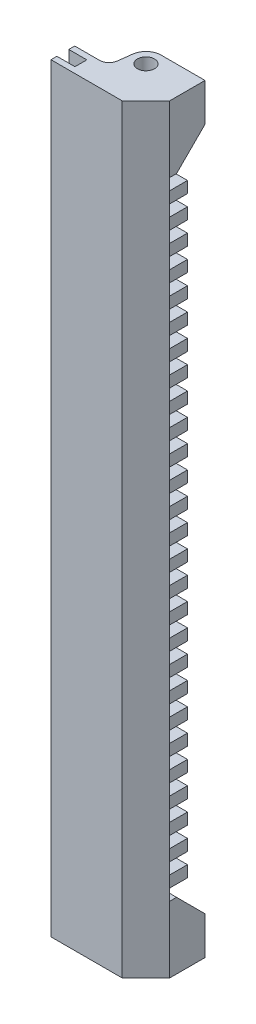
SolidWorks part; units mm, degrees
ref_plane "Front Plane" through (0, 0, 0) normal (0, 0, 1) x (1, 0, 0)
ref_plane "Top Plane" through (0, 0, 0) normal (0, 1, 0) x (1, 0, 0)
ref_plane "Right Plane" through (0, 0, 0) normal (1, 0, 0) x (0, 0, -1)
sketch "Sketch1" plane through (0, 0, 0) normal (0, 1, 0) x (1, 0, 0)
  line L0 (0, 0) -> (25.4, 0)
  line L1 (25.4, 0) -> (25.4, 25.4)
  line L2 (25.4, 25.4) -> (19.05, 25.4)
  line L3 (19.05, 25.4) -> (19.05, 6.35)
  line L4 (19.05, 6.35) -> (0, 6.35)
  line L5 (0, 6.35) -> (0, 0)
  dimension "D1" = 25.4
  dimension "D2" = 6.35
extrude "Boss-Extrude1" add sketch "Sketch1" along normal blind 203.2
sketch "Sketch2" plane through (0, 203.2, 0) normal (0, 1, 0) x (1, 0, 0)
  line L0 (19.05, 25.4) -> (19.05, 6.35) construction
  line L1 (19.05, 6.35) -> (0, 6.35) construction
  line L2 (19.05, 15.8022) -> (19.05, 6.35)
  line L3 (19.05, 6.35) -> (8.89, 6.35)
  line L4 (8.89, 6.35) -> (9.6295, 12.244)
  line L5 (19.05, 15.8022) -> (13.6618, 15.8022)
  line L6 (13.6618, 11.7382) -> (19.05, 6.35) construction
  arc A0 (13.6618, 15.8022) -> (9.6295, 12.244) centre (13.6618, 11.7382) ccw
  circle A1 centre (13.6618, 11.7382) radius 2.286
  dimension "D4" = 4.572
  dimension "D5" = 1.778
  dimension "D1" = 45
  dimension "D3" = 10.16
  dimension "D6" = 7.62
extrude "Boss-Extrude2" add sketch "Sketch2" against normal blind 6.35
ref_plane "Plane1" through (0, 101.6, 0) normal (0, 1, 0) x (1, 0, 0)
fillet "Fillet1" radius 2.54 1 edges at (8.89, 200.025, -6.35)
mirror "Mirror1" about plane through (0, 101.6, 0) normal (0, 1, 0) of "Fillet1", "Boss-Extrude2"
sketch "Sketch5" plane through (0, 203.2, 0) normal (0, 1, 0) x (1, 0, 0)
  line L0 (25.4, 0) -> (25.4, 25.4) construction
  line L1 (19.05, 25.4) -> (25.4, 25.4)
  line L2 (19.05, 25.4) -> (19.05, 15.8022)
  line L3 (19.05, 15.8022) -> (25.4, 15.8022)
  line L4 (25.4, 25.4) -> (25.4, 15.8022)
extrude "Cut-Extrude3" cut sketch "Sketch5" against normal through all
sketch "Sketch4" plane through (0, 0, 0) normal (0, -1, 0) x (1, 0, 0)
  line L0 (0, -6.35) -> (0, 0) construction
  line L1 (0, -1.5875) -> (4.826, -1.5875)
  line L2 (0, -1.5875) -> (0, -4.7625)
  line L3 (0, -4.7625) -> (4.826, -4.7625)
  line L4 (4.826, -1.5875) -> (4.826, -4.7625)
  point P6 (0, -3.175)
  point P7 (0, -3.175)
  dimension "D1" = 3.175
  dimension "D2" = 4.826
extrude "Cut-Extrude2" cut sketch "Sketch4" against normal through all
sketch "Sketch6" plane through (19.05, 0, 0) normal (-1, 0, 0) x (0, 0, 1)
  line L0 (-6.35, 196.85) -> (-6.35, 6.35) construction
  line L1 (-6.35, 17.78) -> (-15.8022, 17.78)
  line L2 (-6.35, 17.78) -> (-6.35, 20.828)
  line L3 (-6.35, 20.828) -> (-15.8022, 20.828)
  line L4 (-15.8022, 17.78) -> (-15.8022, 20.828)
  line L5 (-15.8022, 6.35) -> (-15.8022, 196.85) construction
  line L6 (-6.35, 23.876) -> (-6.35, 26.924)
  line L7 (-6.35, 23.876) -> (-15.8022, 23.876)
  line L8 (-15.8022, 23.876) -> (-15.8022, 26.924)
  line L9 (-6.35, 26.924) -> (-15.8022, 26.924)
  line L10 (-6.35, 29.972) -> (-6.35, 33.02)
  line L11 (-6.35, 29.972) -> (-15.8022, 29.972)
  line L12 (-15.8022, 29.972) -> (-15.8022, 33.02)
  line L13 (-6.35, 33.02) -> (-15.8022, 33.02)
  line L14 (-6.35, 36.068) -> (-6.35, 39.116)
  line L15 (-6.35, 36.068) -> (-15.8022, 36.068)
  line L16 (-15.8022, 36.068) -> (-15.8022, 39.116)
  line L17 (-6.35, 39.116) -> (-15.8022, 39.116)
  line L18 (-6.35, 42.164) -> (-6.35, 45.212)
  line L19 (-6.35, 42.164) -> (-15.8022, 42.164)
  line L20 (-15.8022, 42.164) -> (-15.8022, 45.212)
  line L21 (-6.35, 45.212) -> (-15.8022, 45.212)
  line L22 (-6.35, 48.26) -> (-6.35, 51.308)
  line L23 (-6.35, 48.26) -> (-15.8022, 48.26)
  line L24 (-15.8022, 48.26) -> (-15.8022, 51.308)
  line L25 (-6.35, 51.308) -> (-15.8022, 51.308)
  line L26 (-6.35, 54.356) -> (-6.35, 57.404)
  line L27 (-6.35, 54.356) -> (-15.8022, 54.356)
  line L28 (-15.8022, 54.356) -> (-15.8022, 57.404)
  line L29 (-6.35, 57.404) -> (-15.8022, 57.404)
  line L30 (-6.35, 60.452) -> (-6.35, 63.5)
  line L31 (-6.35, 60.452) -> (-15.8022, 60.452)
  line L32 (-15.8022, 60.452) -> (-15.8022, 63.5)
  line L33 (-6.35, 63.5) -> (-15.8022, 63.5)
  line L34 (-6.35, 66.548) -> (-6.35, 69.596)
  line L35 (-6.35, 66.548) -> (-15.8022, 66.548)
  line L36 (-15.8022, 66.548) -> (-15.8022, 69.596)
  line L37 (-6.35, 69.596) -> (-15.8022, 69.596)
  line L38 (-6.35, 72.644) -> (-6.35, 75.692)
  line L39 (-6.35, 72.644) -> (-15.8022, 72.644)
  line L40 (-15.8022, 72.644) -> (-15.8022, 75.692)
  line L41 (-6.35, 75.692) -> (-15.8022, 75.692)
  line L42 (-6.35, 78.74) -> (-6.35, 81.788)
  line L43 (-6.35, 78.74) -> (-15.8022, 78.74)
  line L44 (-15.8022, 78.74) -> (-15.8022, 81.788)
  line L45 (-6.35, 81.788) -> (-15.8022, 81.788)
  line L46 (-6.35, 84.836) -> (-6.35, 87.884)
  line L47 (-6.35, 84.836) -> (-15.8022, 84.836)
  line L48 (-15.8022, 84.836) -> (-15.8022, 87.884)
  line L49 (-6.35, 87.884) -> (-15.8022, 87.884)
  line L50 (-6.35, 90.932) -> (-6.35, 93.98)
  line L51 (-6.35, 90.932) -> (-15.8022, 90.932)
  line L52 (-15.8022, 90.932) -> (-15.8022, 93.98)
  line L53 (-6.35, 93.98) -> (-15.8022, 93.98)
  line L54 (-6.35, 97.028) -> (-6.35, 100.076)
  line L55 (-6.35, 97.028) -> (-15.8022, 97.028)
  line L56 (-15.8022, 97.028) -> (-15.8022, 100.076)
  line L57 (-6.35, 100.076) -> (-15.8022, 100.076)
  line L58 (-6.35, 103.124) -> (-6.35, 106.172)
  line L59 (-6.35, 103.124) -> (-15.8022, 103.124)
  line L60 (-15.8022, 103.124) -> (-15.8022, 106.172)
  line L61 (-6.35, 106.172) -> (-15.8022, 106.172)
  line L62 (-6.35, 109.22) -> (-6.35, 112.268)
  line L63 (-6.35, 109.22) -> (-15.8022, 109.22)
  line L64 (-15.8022, 109.22) -> (-15.8022, 112.268)
  line L65 (-6.35, 112.268) -> (-15.8022, 112.268)
  line L66 (-6.35, 115.316) -> (-6.35, 118.364)
  line L67 (-6.35, 115.316) -> (-15.8022, 115.316)
  line L68 (-15.8022, 115.316) -> (-15.8022, 118.364)
  line L69 (-6.35, 118.364) -> (-15.8022, 118.364)
  line L70 (-6.35, 121.412) -> (-6.35, 124.46)
  line L71 (-6.35, 121.412) -> (-15.8022, 121.412)
  line L72 (-15.8022, 121.412) -> (-15.8022, 124.46)
  line L73 (-6.35, 124.46) -> (-15.8022, 124.46)
  line L74 (-6.35, 127.508) -> (-6.35, 130.556)
  line L75 (-6.35, 127.508) -> (-15.8022, 127.508)
  line L76 (-15.8022, 127.508) -> (-15.8022, 130.556)
  line L77 (-6.35, 130.556) -> (-15.8022, 130.556)
  line L78 (-6.35, 133.604) -> (-6.35, 136.652)
  line L79 (-6.35, 133.604) -> (-15.8022, 133.604)
  line L80 (-15.8022, 133.604) -> (-15.8022, 136.652)
  line L81 (-6.35, 136.652) -> (-15.8022, 136.652)
  line L82 (-6.35, 139.7) -> (-6.35, 142.748)
  line L83 (-6.35, 139.7) -> (-15.8022, 139.7)
  line L84 (-15.8022, 139.7) -> (-15.8022, 142.748)
  line L85 (-6.35, 142.748) -> (-15.8022, 142.748)
  line L86 (-6.35, 145.796) -> (-6.35, 148.844)
  line L87 (-6.35, 145.796) -> (-15.8022, 145.796)
  line L88 (-15.8022, 145.796) -> (-15.8022, 148.844)
  line L89 (-6.35, 148.844) -> (-15.8022, 148.844)
  line L90 (-6.35, 151.892) -> (-6.35, 154.94)
  line L91 (-6.35, 151.892) -> (-15.8022, 151.892)
  line L92 (-15.8022, 151.892) -> (-15.8022, 154.94)
  line L93 (-6.35, 154.94) -> (-15.8022, 154.94)
  line L94 (-6.35, 157.988) -> (-6.35, 161.036)
  line L95 (-6.35, 157.988) -> (-15.8022, 157.988)
  line L96 (-15.8022, 157.988) -> (-15.8022, 161.036)
  line L97 (-6.35, 161.036) -> (-15.8022, 161.036)
  line L98 (-6.35, 164.084) -> (-6.35, 167.132)
  line L99 (-6.35, 164.084) -> (-15.8022, 164.084)
  line L100 (-15.8022, 164.084) -> (-15.8022, 167.132)
  line L101 (-6.35, 167.132) -> (-15.8022, 167.132)
  line L102 (-6.35, 170.18) -> (-6.35, 173.228)
  line L103 (-6.35, 170.18) -> (-15.8022, 170.18)
  line L104 (-15.8022, 170.18) -> (-15.8022, 173.228)
  line L105 (-6.35, 173.228) -> (-15.8022, 173.228)
  line L106 (-6.35, 176.276) -> (-6.35, 179.324)
  line L107 (-6.35, 176.276) -> (-15.8022, 176.276)
  line L108 (-15.8022, 176.276) -> (-15.8022, 179.324)
  line L109 (-6.35, 179.324) -> (-15.8022, 179.324)
  line L110 (-6.35, 182.372) -> (-6.35, 185.42)
  line L111 (-6.35, 182.372) -> (-15.8022, 182.372)
  line L112 (-15.8022, 182.372) -> (-15.8022, 185.42)
  line L113 (-6.35, 185.42) -> (-15.8022, 185.42)
  line L114 (-15.8022, 17.78) -> (-15.8022, 185.42) construction
  point P8 (-6.35, 101.6)
  point P9 (-15.8022, 101.6)
  dimension "D1" = 3.048
  dimension "D2" = 28
  dimension "D3" = 3.048
extrude "Cut-Extrude4" cut sketch "Sketch6" against normal through all
sketch "Sketch7" plane through (19.05, 0, 0) normal (-1, 0, 0) x (0, 0, 1)
  line L0 (-15.8022, 182.372) -> (-6.35, 182.372) construction
  line L1 (-15.8022, 20.828) -> (-11.1125, 20.828)
  line L2 (-15.8022, 20.828) -> (-15.8022, 182.372)
  line L3 (-15.8022, 182.372) -> (-11.1125, 182.372)
  line L4 (-11.1125, 20.828) -> (-11.1125, 182.372)
  line L5 (-6.35, 182.372) -> (-6.35, 179.324) construction
  dimension "D1" = 4.7625
extrude "Cut-Extrude5" cut sketch "Sketch7" against normal through all
chamfer "Chamfer1" distance 6.35 angle 45 1 edges at (25.4, 101.6, 0)
sketch "Sketch8" plane through (19.05, 0, 0) normal (-1, 0, 0) x (0, 0, 1)
  line L0 (-6.35, 182.372) -> (-11.1125, 182.372) construction
  line L1 (-11.1125, 182.372) -> (-11.1125, 179.324) construction
  line L2 (-11.1125, 179.324) -> (-6.35, 179.324) construction
  line L3 (-6.35, 179.324) -> (-6.35, 182.372) construction
  line L4 (-6.35, 176.276) -> (-11.1125, 176.276) construction
  line L5 (-11.1125, 176.276) -> (-11.1125, 173.228) construction
  line L6 (-11.1125, 173.228) -> (-6.35, 173.228) construction
  line L7 (-6.35, 173.228) -> (-6.35, 176.276) construction
  line L8 (-6.35, 170.18) -> (-11.1125, 170.18) construction
  line L9 (-11.1125, 170.18) -> (-11.1125, 167.132) construction
  line L10 (-11.1125, 167.132) -> (-6.35, 167.132) construction
  line L11 (-6.35, 167.132) -> (-6.35, 170.18) construction
  line L12 (-6.35, 164.084) -> (-11.1125, 164.084) construction
  line L13 (-11.1125, 164.084) -> (-11.1125, 161.036) construction
  line L14 (-11.1125, 161.036) -> (-6.35, 161.036) construction
  line L15 (-6.35, 161.036) -> (-6.35, 164.084) construction
  line L16 (-6.35, 157.988) -> (-11.1125, 157.988) construction
  line L17 (-11.1125, 157.988) -> (-11.1125, 154.94) construction
  line L18 (-11.1125, 154.94) -> (-6.35, 154.94) construction
  line L19 (-6.35, 154.94) -> (-6.35, 157.988) construction
  line L20 (-6.35, 151.892) -> (-11.1125, 151.892) construction
  line L21 (-11.1125, 151.892) -> (-11.1125, 148.844) construction
  line L22 (-11.1125, 148.844) -> (-6.35, 148.844) construction
  line L23 (-6.35, 148.844) -> (-6.35, 151.892) construction
  line L24 (-6.35, 145.796) -> (-11.1125, 145.796) construction
  line L25 (-11.1125, 145.796) -> (-11.1125, 142.748) construction
  line L26 (-11.1125, 142.748) -> (-6.35, 142.748) construction
  line L27 (-6.35, 142.748) -> (-6.35, 145.796) construction
  line L28 (-6.35, 139.7) -> (-11.1125, 139.7) construction
  line L29 (-11.1125, 139.7) -> (-11.1125, 136.652) construction
  line L30 (-11.1125, 136.652) -> (-6.35, 136.652) construction
  line L31 (-6.35, 136.652) -> (-6.35, 139.7) construction
  line L32 (-6.35, 133.604) -> (-11.1125, 133.604) construction
  line L33 (-11.1125, 133.604) -> (-11.1125, 130.556) construction
  line L34 (-11.1125, 130.556) -> (-6.35, 130.556) construction
  line L35 (-6.35, 130.556) -> (-6.35, 133.604) construction
  line L36 (-6.35, 127.508) -> (-11.1125, 127.508) construction
  line L37 (-11.1125, 127.508) -> (-11.1125, 124.46) construction
  line L38 (-11.1125, 124.46) -> (-6.35, 124.46) construction
  line L39 (-6.35, 124.46) -> (-6.35, 127.508) construction
  line L40 (-6.35, 121.412) -> (-11.1125, 121.412) construction
  line L41 (-11.1125, 121.412) -> (-11.1125, 118.364) construction
  line L42 (-11.1125, 118.364) -> (-6.35, 118.364) construction
  line L43 (-6.35, 118.364) -> (-6.35, 121.412) construction
  line L44 (-6.35, 115.316) -> (-11.1125, 115.316) construction
  line L45 (-11.1125, 115.316) -> (-11.1125, 112.268) construction
  line L46 (-11.1125, 112.268) -> (-6.35, 112.268) construction
  line L47 (-6.35, 112.268) -> (-6.35, 115.316) construction
  line L48 (-6.35, 109.22) -> (-11.1125, 109.22) construction
  line L49 (-11.1125, 109.22) -> (-11.1125, 106.172) construction
  line L50 (-11.1125, 106.172) -> (-6.35, 106.172) construction
  line L51 (-6.35, 106.172) -> (-6.35, 109.22) construction
  line L52 (-6.35, 103.124) -> (-11.1125, 103.124) construction
  line L53 (-11.1125, 103.124) -> (-11.1125, 100.076) construction
  line L54 (-11.1125, 100.076) -> (-6.35, 100.076) construction
  line L55 (-6.35, 100.076) -> (-6.35, 103.124) construction
  line L56 (-6.35, 97.028) -> (-11.1125, 97.028) construction
  line L57 (-11.1125, 97.028) -> (-11.1125, 93.98) construction
  line L58 (-11.1125, 93.98) -> (-6.35, 93.98) construction
  line L59 (-6.35, 93.98) -> (-6.35, 97.028) construction
  line L60 (-6.35, 90.932) -> (-11.1125, 90.932) construction
  line L61 (-11.1125, 90.932) -> (-11.1125, 87.884) construction
  line L62 (-11.1125, 87.884) -> (-6.35, 87.884) construction
  line L63 (-6.35, 87.884) -> (-6.35, 90.932) construction
  line L64 (-6.35, 84.836) -> (-11.1125, 84.836) construction
  line L65 (-11.1125, 84.836) -> (-11.1125, 81.788) construction
  line L66 (-11.1125, 81.788) -> (-6.35, 81.788) construction
  line L67 (-6.35, 81.788) -> (-6.35, 84.836) construction
  line L68 (-6.35, 78.74) -> (-11.1125, 78.74) construction
  line L69 (-11.1125, 78.74) -> (-11.1125, 75.692) construction
  line L70 (-11.1125, 75.692) -> (-6.35, 75.692) construction
  line L71 (-6.35, 75.692) -> (-6.35, 78.74) construction
  line L72 (-6.35, 72.644) -> (-11.1125, 72.644) construction
  line L73 (-11.1125, 72.644) -> (-11.1125, 69.596) construction
  line L74 (-11.1125, 69.596) -> (-6.35, 69.596) construction
  line L75 (-6.35, 69.596) -> (-6.35, 72.644) construction
  line L76 (-6.35, 66.548) -> (-11.1125, 66.548) construction
  line L77 (-11.1125, 66.548) -> (-11.1125, 63.5) construction
  line L78 (-11.1125, 63.5) -> (-6.35, 63.5) construction
  line L79 (-6.35, 63.5) -> (-6.35, 66.548) construction
  line L80 (-6.35, 60.452) -> (-11.1125, 60.452) construction
  line L81 (-11.1125, 60.452) -> (-11.1125, 57.404) construction
  line L82 (-11.1125, 57.404) -> (-6.35, 57.404) construction
  line L83 (-6.35, 57.404) -> (-6.35, 60.452) construction
  line L84 (-6.35, 54.356) -> (-11.1125, 54.356) construction
  line L85 (-11.1125, 54.356) -> (-11.1125, 51.308) construction
  line L86 (-11.1125, 51.308) -> (-6.35, 51.308) construction
  line L87 (-6.35, 51.308) -> (-6.35, 54.356) construction
  line L88 (-6.35, 48.26) -> (-11.1125, 48.26) construction
  line L89 (-11.1125, 48.26) -> (-11.1125, 45.212) construction
  line L90 (-11.1125, 45.212) -> (-6.35, 45.212) construction
  line L91 (-6.35, 45.212) -> (-6.35, 48.26) construction
  line L92 (-6.35, 42.164) -> (-11.1125, 42.164) construction
  line L93 (-11.1125, 42.164) -> (-11.1125, 39.116) construction
  line L94 (-11.1125, 39.116) -> (-6.35, 39.116) construction
  line L95 (-6.35, 39.116) -> (-6.35, 42.164) construction
  line L96 (-6.35, 36.068) -> (-11.1125, 36.068) construction
  line L97 (-11.1125, 36.068) -> (-11.1125, 33.02) construction
  line L98 (-11.1125, 33.02) -> (-6.35, 33.02) construction
  line L99 (-6.35, 33.02) -> (-6.35, 36.068) construction
  line L100 (-6.35, 29.972) -> (-11.1125, 29.972) construction
  line L101 (-11.1125, 29.972) -> (-11.1125, 26.924) construction
  line L102 (-11.1125, 26.924) -> (-6.35, 26.924) construction
  line L103 (-6.35, 26.924) -> (-6.35, 29.972) construction
  line L104 (-6.35, 23.876) -> (-11.1125, 23.876) construction
  line L105 (-11.1125, 23.876) -> (-11.1125, 20.828) construction
  line L106 (-11.1125, 20.828) -> (-6.35, 20.828) construction
  line L107 (-6.35, 20.828) -> (-6.35, 23.876) construction
  line L108 (-6.35, 182.372) -> (-11.1125, 182.372)
  line L109 (-11.1125, 182.372) -> (-11.1125, 179.324)
  line L110 (-11.1125, 179.324) -> (-6.35, 179.324)
  line L111 (-6.35, 179.324) -> (-6.35, 182.372)
  line L112 (-6.35, 176.276) -> (-11.1125, 176.276)
  line L113 (-11.1125, 176.276) -> (-11.1125, 173.228)
  line L114 (-11.1125, 173.228) -> (-6.35, 173.228)
  line L115 (-6.35, 173.228) -> (-6.35, 176.276)
  line L116 (-6.35, 170.18) -> (-11.1125, 170.18)
  line L117 (-11.1125, 170.18) -> (-11.1125, 167.132)
  line L118 (-11.1125, 167.132) -> (-6.35, 167.132)
  line L119 (-6.35, 167.132) -> (-6.35, 170.18)
  line L120 (-6.35, 164.084) -> (-11.1125, 164.084)
  line L121 (-11.1125, 164.084) -> (-11.1125, 161.036)
  line L122 (-11.1125, 161.036) -> (-6.35, 161.036)
  line L123 (-6.35, 161.036) -> (-6.35, 164.084)
  line L124 (-6.35, 157.988) -> (-11.1125, 157.988)
  line L125 (-11.1125, 157.988) -> (-11.1125, 154.94)
  line L126 (-11.1125, 154.94) -> (-6.35, 154.94)
  line L127 (-6.35, 154.94) -> (-6.35, 157.988)
  line L128 (-6.35, 151.892) -> (-11.1125, 151.892)
  line L129 (-11.1125, 151.892) -> (-11.1125, 148.844)
  line L130 (-11.1125, 148.844) -> (-6.35, 148.844)
  line L131 (-6.35, 148.844) -> (-6.35, 151.892)
  line L132 (-6.35, 145.796) -> (-11.1125, 145.796)
  line L133 (-11.1125, 145.796) -> (-11.1125, 142.748)
  line L134 (-11.1125, 142.748) -> (-6.35, 142.748)
  line L135 (-6.35, 142.748) -> (-6.35, 145.796)
  line L136 (-6.35, 139.7) -> (-11.1125, 139.7)
  line L137 (-11.1125, 139.7) -> (-11.1125, 136.652)
  line L138 (-11.1125, 136.652) -> (-6.35, 136.652)
  line L139 (-6.35, 136.652) -> (-6.35, 139.7)
  line L140 (-6.35, 133.604) -> (-11.1125, 133.604)
  line L141 (-11.1125, 133.604) -> (-11.1125, 130.556)
  line L142 (-11.1125, 130.556) -> (-6.35, 130.556)
  line L143 (-6.35, 130.556) -> (-6.35, 133.604)
  line L144 (-6.35, 127.508) -> (-11.1125, 127.508)
  line L145 (-11.1125, 127.508) -> (-11.1125, 124.46)
  line L146 (-11.1125, 124.46) -> (-6.35, 124.46)
  line L147 (-6.35, 124.46) -> (-6.35, 127.508)
  line L148 (-6.35, 121.412) -> (-11.1125, 121.412)
  line L149 (-11.1125, 121.412) -> (-11.1125, 118.364)
  line L150 (-11.1125, 118.364) -> (-6.35, 118.364)
  line L151 (-6.35, 118.364) -> (-6.35, 121.412)
  line L152 (-6.35, 115.316) -> (-11.1125, 115.316)
  line L153 (-11.1125, 115.316) -> (-11.1125, 112.268)
  line L154 (-11.1125, 112.268) -> (-6.35, 112.268)
  line L155 (-6.35, 112.268) -> (-6.35, 115.316)
  line L156 (-6.35, 109.22) -> (-11.1125, 109.22)
  line L157 (-11.1125, 109.22) -> (-11.1125, 106.172)
  line L158 (-11.1125, 106.172) -> (-6.35, 106.172)
  line L159 (-6.35, 106.172) -> (-6.35, 109.22)
  line L160 (-6.35, 103.124) -> (-11.1125, 103.124)
  line L161 (-11.1125, 103.124) -> (-11.1125, 100.076)
  line L162 (-11.1125, 100.076) -> (-6.35, 100.076)
  line L163 (-6.35, 100.076) -> (-6.35, 103.124)
  line L164 (-6.35, 97.028) -> (-11.1125, 97.028)
  line L165 (-11.1125, 97.028) -> (-11.1125, 93.98)
  line L166 (-11.1125, 93.98) -> (-6.35, 93.98)
  line L167 (-6.35, 93.98) -> (-6.35, 97.028)
  line L168 (-6.35, 90.932) -> (-11.1125, 90.932)
  line L169 (-11.1125, 90.932) -> (-11.1125, 87.884)
  line L170 (-11.1125, 87.884) -> (-6.35, 87.884)
  line L171 (-6.35, 87.884) -> (-6.35, 90.932)
  line L172 (-6.35, 84.836) -> (-11.1125, 84.836)
  line L173 (-11.1125, 84.836) -> (-11.1125, 81.788)
  line L174 (-11.1125, 81.788) -> (-6.35, 81.788)
  line L175 (-6.35, 81.788) -> (-6.35, 84.836)
  line L176 (-6.35, 78.74) -> (-11.1125, 78.74)
  line L177 (-11.1125, 78.74) -> (-11.1125, 75.692)
  line L178 (-11.1125, 75.692) -> (-6.35, 75.692)
  line L179 (-6.35, 75.692) -> (-6.35, 78.74)
  line L180 (-6.35, 72.644) -> (-11.1125, 72.644)
  line L181 (-11.1125, 72.644) -> (-11.1125, 69.596)
  line L182 (-11.1125, 69.596) -> (-6.35, 69.596)
  line L183 (-6.35, 69.596) -> (-6.35, 72.644)
  line L184 (-6.35, 66.548) -> (-11.1125, 66.548)
  line L185 (-11.1125, 66.548) -> (-11.1125, 63.5)
  line L186 (-11.1125, 63.5) -> (-6.35, 63.5)
  line L187 (-6.35, 63.5) -> (-6.35, 66.548)
  line L188 (-6.35, 60.452) -> (-11.1125, 60.452)
  line L189 (-11.1125, 60.452) -> (-11.1125, 57.404)
  line L190 (-11.1125, 57.404) -> (-6.35, 57.404)
  line L191 (-6.35, 57.404) -> (-6.35, 60.452)
  line L192 (-6.35, 54.356) -> (-11.1125, 54.356)
  line L193 (-11.1125, 54.356) -> (-11.1125, 51.308)
  line L194 (-11.1125, 51.308) -> (-6.35, 51.308)
  line L195 (-6.35, 51.308) -> (-6.35, 54.356)
  line L196 (-6.35, 48.26) -> (-11.1125, 48.26)
  line L197 (-11.1125, 48.26) -> (-11.1125, 45.212)
  line L198 (-11.1125, 45.212) -> (-6.35, 45.212)
  line L199 (-6.35, 45.212) -> (-6.35, 48.26)
  line L200 (-6.35, 42.164) -> (-11.1125, 42.164)
  line L201 (-11.1125, 42.164) -> (-11.1125, 39.116)
  line L202 (-11.1125, 39.116) -> (-6.35, 39.116)
  line L203 (-6.35, 39.116) -> (-6.35, 42.164)
  line L204 (-6.35, 36.068) -> (-11.1125, 36.068)
  line L205 (-11.1125, 36.068) -> (-11.1125, 33.02)
  line L206 (-11.1125, 33.02) -> (-6.35, 33.02)
  line L207 (-6.35, 33.02) -> (-6.35, 36.068)
  line L208 (-6.35, 29.972) -> (-11.1125, 29.972)
  line L209 (-11.1125, 29.972) -> (-11.1125, 26.924)
  line L210 (-11.1125, 26.924) -> (-6.35, 26.924)
  line L211 (-6.35, 26.924) -> (-6.35, 29.972)
  line L212 (-6.35, 23.876) -> (-11.1125, 23.876)
  line L213 (-11.1125, 23.876) -> (-11.1125, 20.828)
  line L214 (-11.1125, 20.828) -> (-6.35, 20.828)
  line L215 (-6.35, 20.828) -> (-6.35, 23.876)
extrude "Boss-Extrude3" add sketch "Sketch8" along normal up to surface (19.05 mm away) up to face at (0, 101.6, -5.5563)
chamfer "Chamfer2" distance 1.27 angle 45 4 edges at (19.05, 196.85, -11.0761) (12.8494, 196.85, -6.35) (19.05, 6.35, -11.0761) (12.8494, 6.35, -6.35)
chamfer "Chamfer3" distance 7.62 angle 45 2 edges at (22.225, 185.42, -15.8022) (22.225, 17.78, -15.8022)
